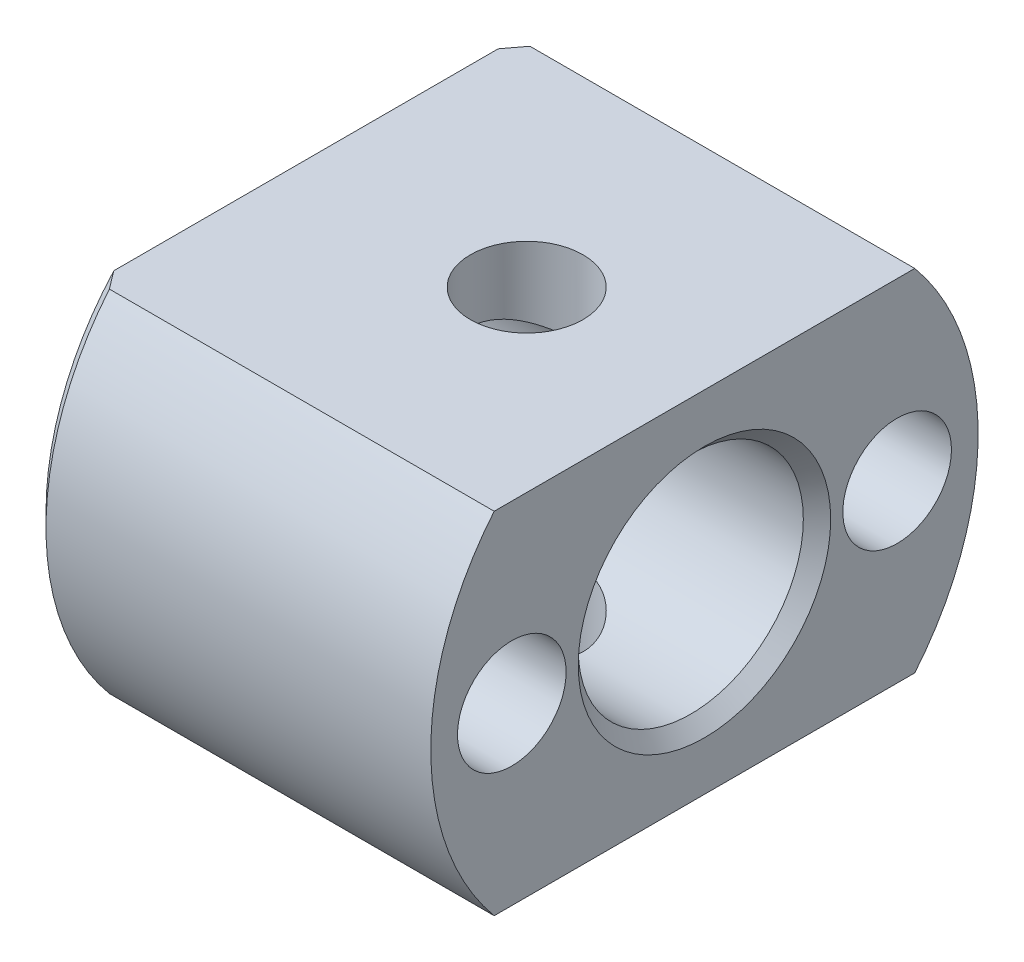
SolidWorks part; units mm, degrees
ref_plane "Front Plane" through (0, 0, 0) normal (0, 0, 1) x (1, 0, 0)
ref_plane "Top Plane" through (0, 0, 0) normal (0, 1, 0) x (1, 0, 0)
ref_plane "Right Plane" through (0, 0, 0) normal (1, 0, 0) x (0, 0, -1)
sketch "Sketch1" plane through (0, 0, 0) normal (1, 0, 0) x (0, 0, -1)
  line L0 (0, 0) -> (0, 0.7417) construction
  line L1 (-3.2639, 0) -> (-6.35, 0) construction
  circle A0 centre (0, 0) radius 6.35
  circle A1 centre (0, 0) radius 6.35
  circle A2 centre (0, 0) radius 3.2639
  circle A3 centre (-5.588, 0) radius 1.575
  circle A5 centre (0, 0) radius 7.9375
  circle A6 centre (5.588, 0) radius 1.575
  dimension "D1" = 12.7
  dimension "D2" = 6.5278
  dimension "D3" = 3.15
  dimension "D4" = 15.875
  dimension "D5" = 11.176
extrude "Inner Side Extrude" add sketch "Sketch1" along normal blind 2.032 contours A0 A2 A3 A6 | A5 A1 A6 A3 region at (0, 0, -3.8358) region at (0, 0, 7.713)
extrude "Outer Side Extrude" add sketch "Sketch1<3>" against normal blind 9.525 contours A0 A2 A3 A6 | A5 A0 region at (0, 0, -3.8358) region at (0, 0, 7.713)
sketch "Sketch1<3>" plane through (0, 0, 0) normal (1, 0, 0) x (0, 0, -1) same geometry as "Sketch1"
sketch "Sketch2" plane through (0, 0, 0) normal (0, 1, 0) x (1, 0, 0)
  line L0 (-9.525, 7.9375) -> (-9.525, -7.9375) construction
  line L1 (-9.525, 0) -> (0, 0) construction
  line L2 (2.032, -7.9375) -> (2.032, 7.9375) construction
  circle A0 centre (-3.1242, 0) radius 1.632
  point P0 (-9.525, 0)
  point P8 (0, 0)
  dimension "D1" = 3.2639
  dimension "D2" = 5.1562
extrude "Clevis Pin Cut" cut sketch "Sketch2" against normal through all and the other way through all
chamfer "Chamfer so Steve Doesn't cut himself" distance 0.3969 angle 45 3 edges at (-9.525, 0, -3.2639) (2.032, 0, -3.2639) (-9.525, 0, -7.9375)
sketch "Sketch4" plane through (0, 0, 0) normal (0, 0, 1) x (1, 0, 0)
  line L0 (-3.1242, -5.08) -> (-3.1242, 5.08)
  line L1 (-12.6492, 9.8837) -> (6.4008, 9.8837)
  line L2 (-12.6492, 9.8837) -> (-12.6492, 5.08)
  line L3 (-12.6492, 5.08) -> (6.4008, 5.08)
  line L4 (6.4008, 9.8837) -> (6.4008, 5.08)
  line L5 (-1.4923, 0) -> (-4.7562, 0) construction
  line L6 (6.3564, 0) -> (-6.3564, 0) construction
  line L7 (6.4008, -9.8837) -> (6.4008, -5.08)
  line L8 (-12.6492, -5.08) -> (6.4008, -5.08)
  line L9 (-12.6492, -9.8837) -> (-12.6492, -5.08)
  line L10 (-12.6492, -9.8837) -> (6.4008, -9.8837)
  point P8 (0, 0)
  point P17 (-3.1242, 0)
  dimension "D1" = 19.05
  dimension "D2" = 5.08
extrude "Cut-Extrude1" cut sketch "Sketch4" against normal through all both and the other way through all contours L9 L10 L7 L8 | L4 L1 L2 L3 region at (-3.1242, 7.4819, 0) region at (-3.1242, -7.4819, 0)
